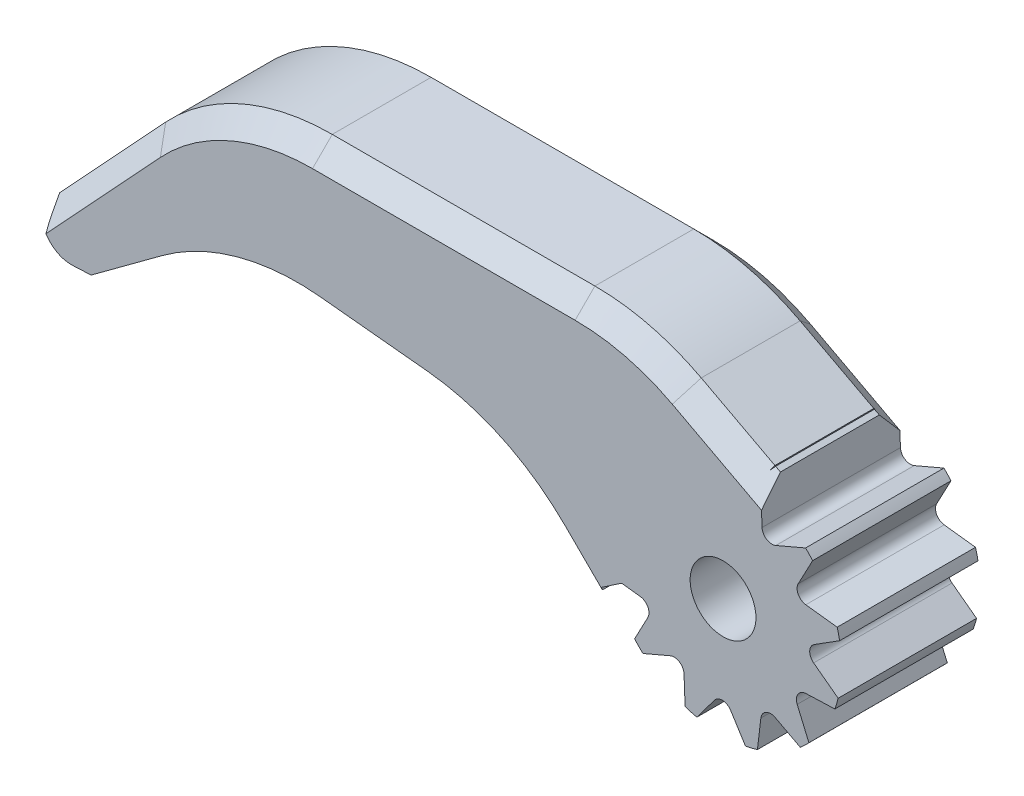
SolidWorks part; units mm, degrees
ref_plane "前视基准面" through (0, 0, 0) normal (0, 0, 1) x (1, 0, 0)
ref_plane "上视基准面" through (0, 0, 0) normal (0, 1, 0) x (1, 0, 0)
ref_plane "右视基准面" through (0, 0, 0) normal (1, 0, 0) x (0, 0, -1)
sketch "Sketch1" plane through (0, 0, 0) normal (1, 0, 0) x (0, 0, -1)
  line L1 (-14.76, 15.6242) -> (2.04, 15.6242)
  line L2 (-14.76, 15.6242) -> (-14.76, -2.5758)
  line L3 (-14.76, -2.5758) -> (2.04, -2.5758)
  line L4 (2.04, 15.6242) -> (2.04, -2.5758)
  line L5 (-14.76, 15.6242) -> (2.04, -2.5758) construction
  line L6 (-14.76, -2.5758) -> (2.04, 15.6242) construction
  point P0 (-6.36, 6.5242)
  dimension "D1" = 16.8
  dimension "D2" = 18.2
extrude "Boss-Extrude1" add sketch "Sketch1" along normal blind 7.91
sketch "Sketch2" plane through (7.91, 0, 0) normal (1, 0, 0) x (0, 0, -1)
  line L0 (2.04, -2.5758) -> (2.04, 15.6242) construction
  line L1 (-9.47, 19.1945) -> (-8.47, 19.1945)
  line L2 (-9.47, 19.1945) -> (-9.47, -5.8055)
  line L3 (-9.47, -5.8055) -> (-8.47, -5.8055)
  line L4 (-8.47, 19.1945) -> (-8.47, -5.8055)
  dimension "D1" = 10.51
  dimension "D2" = 1
  dimension "D3" = 25
extrude "Boss-Extrude2" add sketch "Sketch2" against normal up to surface (7.91 mm away) contours L1 L4 L3 L2 up to face at (0, 6.5242, 6.36)
sketch "Sketch3" plane through (0, 0, 9.47) normal (0, 0, 1) x (1, 0, 0)
  line L0 (0, 15.6242) -> (0, -2.5758) construction
  line L1 (-3.955, -4.4308) -> (3.955, -4.4308) construction
  line L2 (-3.955, -4.4308) -> (-3.955, 17.4792) construction
  line L3 (-3.955, 17.4792) -> (3.955, 17.4792) construction
  line L4 (3.955, -4.4308) -> (3.955, 17.4792) construction
  line L5 (-3.955, -4.4308) -> (3.955, 17.4792) construction
  line L6 (-3.955, 17.4792) -> (3.955, -4.4308) construction
  circle A0 centre (3.955, 17.4792) radius 1
  circle A1 centre (3.955, -4.4308) radius 1
  point P0 (0, 6.5242)
  dimension "D1" = 21.91
extrude "Cut-Extrude1" cut sketch "Sketch3" against normal blind 21.9
sketch "Sketch4" plane through (0, 0, 14.76) normal (0, 0, 1) x (1, 0, 0)
  circle A0 centre (3.955, 11.3332) radius 1.9516
extrude "Boss-Extrude3" add sketch "Sketch4" along normal blind 3
sketch "Sketch5" plane through (0, 0, 17.76) normal (0, 0, 1) x (1, 0, 0)
  line L0 (3.955, 5.1286) -> (-1.9792, 5.1286) construction
  line L1 (-28.0129, 9.5262) -> (-30.248, 9.4243)
  line L2 (-30.6067, 11.3332) -> (-30.248, 9.4243)
  line L4 (-28.0129, 9.5262) -> (-20.8412, 14.8166)
  line L10 (-21.8292, 20.7912) -> (-30.6067, 11.3332)
  line L11 (-20.8412, 14.8166) -> (-6.9323, 13.416)
  line L12 (-6.9323, 13.416) -> (-0.6973, 7.228)
  line L13 (-21.8292, 20.7912) -> (-0.6713, 20.7912)
  line L14 (-0.6713, 20.7912) -> (6.545, 16.9714)
  circle A0 centre (3.955, 11.3332) radius 3.1
  circle A1 centre (3.955, 11.3332) radius 6.2046 construction
  arc A2 (-0.6973, 7.228) -> (6.545, 16.9714) centre (3.955, 11.3332) ccw
  dimension "D1" = 12.4092
  dimension "D2" = 6.2
extrude "Boss-Extrude4" add sketch "Sketch5" along normal blind 7 separate body
sketch "Sketch6" plane through (0, 0, 0) normal (-1, 0, 0) x (0, 0, 1)
  line L0 (17.76, 22.7282) -> (-5.1444, 21.9553)
  line L1 (-5.1444, 21.9553) -> (-2.936, -7.1287)
  line L2 (-2.936, -7.1287) -> (17.0897, -7.5405)
  line L3 (17.0897, -7.5405) -> (17.76, 5.9646)
  line L4 (17.76, 5.9646) -> (17.76, 22.7282)
extrude "Cut-Extrude2" cut sketch "Sketch6" against normal through all both and the other way through all
sketch "Sketch7" plane through (0, 0, 24.76) normal (0, 0, 1) x (1, 0, 0)
  line L0 (3.955, 7.2492) -> (2.0258, 4.6734)
  line L43 (3.955, 11.3332) -> (3.955, 22.9571) construction
  line L45 (2.0258, 4.6734) -> (5.5723, 4.6734)
  line L46 (5.5723, 4.6734) -> (3.955, 7.2492)
  line L47 (1.955, 7.7851) -> (-1.0037, 6.519)
  line L48 (-1.0037, 6.519) -> (2.0678, 4.7457)
  line L49 (2.0678, 4.7457) -> (1.955, 7.7851)
  line L50 (0.4909, 9.2492) -> (-2.7044, 9.6321)
  line L51 (-2.7044, 9.6321) -> (-0.9311, 6.5607)
  line L52 (-0.9311, 6.5607) -> (0.4909, 9.2492)
  line L53 (-0.045, 11.2492) -> (-2.6208, 13.1784)
  line L54 (-2.6208, 13.1784) -> (-2.6208, 9.6319)
  line L55 (-2.6208, 9.6319) -> (-0.045, 11.2492)
  line L56 (0.4909, 13.2492) -> (-0.7752, 16.2079)
  line L57 (-0.7752, 16.2079) -> (-2.5485, 13.1365)
  line L58 (-2.5485, 13.1365) -> (0.4909, 13.2492)
  line L59 (1.955, 14.7133) -> (2.3379, 17.9086)
  line L60 (2.3379, 17.9086) -> (-0.7336, 16.1354)
  line L61 (-0.7336, 16.1354) -> (1.955, 14.7133)
  line L62 (3.955, 15.2492) -> (5.8842, 17.825)
  line L63 (5.8842, 17.825) -> (2.3377, 17.825)
  line L64 (2.3377, 17.825) -> (3.955, 15.2492)
  line L65 (5.955, 14.7133) -> (8.9137, 15.9794)
  line L66 (8.9137, 15.9794) -> (5.8422, 17.7527)
  line L67 (5.8422, 17.7527) -> (5.955, 14.7133)
  line L68 (7.4191, 13.2492) -> (10.6144, 12.8664)
  line L69 (10.6144, 12.8664) -> (8.8411, 15.9378)
  line L70 (8.8411, 15.9378) -> (7.4191, 13.2492)
  line L71 (7.955, 11.2492) -> (10.5308, 9.32)
  line L72 (10.5308, 9.32) -> (10.5308, 12.8666)
  line L73 (10.5308, 12.8666) -> (7.955, 11.2492)
  line L74 (7.4191, 9.2492) -> (8.6852, 6.2905)
  line L75 (8.6852, 6.2905) -> (10.4585, 9.362)
  line L76 (10.4585, 9.362) -> (7.4191, 9.2492)
  line L77 (5.955, 7.7851) -> (5.5721, 4.5898)
  line L78 (5.5721, 4.5898) -> (8.6436, 6.3631)
  line L79 (8.6436, 6.3631) -> (5.955, 7.7851)
  line L80 (3.955, 11.2492) -> (3.955, 7.2492) construction
  dimension "D1" = 4
  dimension "D2" = 12
extrude "Cut-Extrude4" cut sketch "Sketch7" against normal through all both and the other way through all
sketch "Sketch8" plane through (0, 0, 24.76) normal (0, 0, 1) x (1, 0, 0)
  line L0 (-3.5021, 10.0116) -> (-2.2193, 8.7384)
  line L1 (-6.9323, 13.416) -> (-2.1472, 8.6669) construction
  line L2 (-2.2193, 8.7384) -> (0.1979, 10.3812)
  line L3 (0.1979, 10.3812) -> (1.3389, 13.6065)
  line L4 (1.3389, 13.6065) -> (4.5622, 15.1451)
  line L5 (4.5622, 15.1451) -> (5.5802, 17.4821)
  line L6 (5.5802, 17.4821) -> (4.3742, 18.1205)
  line L7 (4.3742, 18.1205) -> (-1.0107, 19.4519)
  line L8 (-1.0107, 19.4519) -> (-5.403, 15.0263)
  line L9 (-5.403, 15.0263) -> (-3.5021, 10.0116)
extrude "Boss-Extrude5" add sketch "Sketch8" against normal up to surface (7 mm away) up to face at (1.1864, 16.2524, 17.76)
sketch "Sketch9" plane through (0, 0, 24.76) normal (0, 0, 1) x (1, 0, 0)
  line L0 (7.1352, 16.421) -> (9.02, 17.6945)
  line L1 (9.02, 17.6945) -> (14.8735, 11.751)
  line L2 (14.8735, 11.751) -> (2.5688, 0.7621)
  line L3 (2.5688, 0.7621) -> (-5.0047, 1.9827)
  line L4 (-5.0047, 1.9827) -> (-6.9744, 6.5878)
  line L5 (-6.9744, 6.5878) -> (-1.1569, 8.1918)
  circle A0 centre (3.955, 11.3332) radius 6 construction
  arc A1 (-1.1569, 8.1918) -> (7.1352, 16.421) centre (3.955, 11.3332) ccw
  dimension "D1" = 6
extrude "Cut-Extrude5" cut sketch "Sketch9" against normal through all both and the other way through all
fillet "Fillet1" radius 0.5 8 edges at (5.955, 14.7133, 21.26) (7.4191, 13.2492, 21.26) (7.955, 11.2492, 21.26) (7.4191, 9.2492, 21.26) (5.955, 7.7851, 21.26) (0.4909, 9.2492, 21.26) (1.955, 7.7851, 21.26) (3.955, 7.2492, 21.26)
fillet "Fillet2" radius 0.8 rebuild error yes
sketch "Sketch10" plane through (0, 0, 17.76) normal (0, 0, -1) x (-1, 0, 0)
  line L0 (-3.955, 11.3332) -> (3.9789, 17.681) construction
  line L1 (2.7294, 19.2427) -> (-5.2045, 12.8949)
  line L2 (2.7294, 19.2427) -> (5.2283, 16.1193)
  line L3 (-5.2045, 12.8949) -> (-2.7055, 9.7715)
  line L4 (5.2283, 16.1193) -> (-2.7055, 9.7715)
  line L5 (2.7294, 19.2427) -> (-2.7055, 9.7715) construction
  line L6 (-5.2045, 12.8949) -> (5.2283, 16.1193) construction
  point P4 (0.0119, 14.5071)
  dimension "D1" = 4
extrude "Cut-Extrude6" cut sketch "Sketch10" against normal offset from surface (3 mm away) 4 up to face at (7.055, 11.3332, 24.76)
fillet "Fillet3" radius 1.5 1 edges at (-30.248, 9.4243, 21.26)
fillet "Fillet4" radius 11.5 4 edges at (-6.9323, 13.416, 21.26) (-20.8412, 14.8166, 21.26) (-0.6713, 20.7912, 21.26) (-21.8292, 20.7912, 21.26)
chamfer "Chamfer1" distance 1 angle 45 8 edges at (-0.7555, 20.4522, 17.76) (-10.1698, 20.7912, 17.76) (-21.4107, 19.8319, 17.76) (-27.9242, 14.2236, 17.76) (-27.9242, 14.2236, 24.76) (-0.7555, 20.4522, 24.76) (-21.4107, 19.8319, 24.76) (-10.1698, 20.7912, 24.76)
sketch "Sketch11" plane through (0, 0, 24.76) normal (0, 0, 1) x (1, 0, 0)
  circle A0 centre (3.955, 11.3332) radius 3.1
  circle A1 centre (3.955, 11.3332) radius 1.6647
extrude "Boss-Extrude6" add sketch "Sketch11" against normal blind 3.5
equation "\"16。8\"=83.7992"
